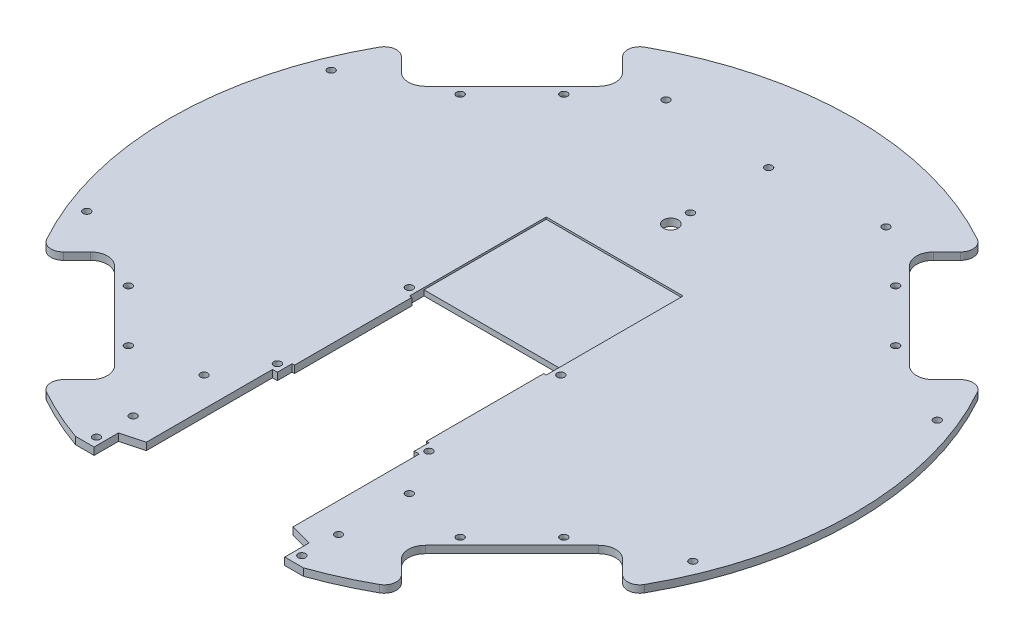
SolidWorks part; units mm, degrees
material "1060 Alloy"
ref_plane "Front Plane" through (0, 0, 0) normal (0, 0, 1) x (1, 0, 0)
ref_plane "Top Plane" through (0, 0, 0) normal (0, 1, 0) x (1, 0, 0)
ref_plane "Right Plane" through (0, 0, 0) normal (1, 0, 0) x (0, 0, -1)
sketch "Sketch1" plane through (0, 0, 0) normal (0, 1, 0) x (1, 0, 0)
  circle A0 centre (0, 0) radius 140
  dimension "D1" = 280
extrude "Boss-Extrude1" add sketch "Sketch1" along normal blind 3
sketch "Sketch7" plane through (0, 3, 0) normal (0, 1, 0) x (1, 0, 0)
  line L0 (-99.0303, -63.6043) -> (-63.6043, -99.0303)
  line L1 (-108.8591, -63.6043) -> (-121.6224, -76.3675)
  line L2 (-63.6043, -108.8591) -> (-76.3675, -121.6224)
  line L3 (-121.6224, -76.3675) -> (-76.3675, -121.6224)
  line L4 (0, 0) -> (-98.9949, -98.9949) construction
  line L7 (0, 0) -> (0, 130) construction
  circle A0 centre (0, 0) radius 140 construction
  arc A1 (-108.8591, -63.6043) -> (-99.0303, -63.6043) centre (-103.9447, -68.5186) cw
  arc A2 (-63.6043, -99.0303) -> (-63.6043, -108.8591) centre (-68.5186, -103.9447) cw
  dimension "D4" = 6.95
  dimension "D1" = 115
  dimension "D2" = 64
  dimension "D3" = 135
extrude "Cut-Extrude4" cut sketch "Sketch7" against normal up to next
sketch "Sketch9" plane through (0, 3, 0) normal (0, 1, 0) x (1, 0, 0)
  line L1 (-63.6043, -99.0303) -> (-99.0303, -63.6043) construction
  line L4 (-108.8591, -63.6043) -> (-119.0017, -73.7469) construction
  circle A0 centre (-89.0955, -67.8823) radius 1.5
  circle A1 centre (-67.8823, -89.0955) radius 1.5
  dimension "D4" = 3
  dimension "D1" = 4
  dimension "D2" = 30
  dimension "D3" = 17
  dimension "D5" = 4
extrude "Cut-Extrude6" cut sketch "Sketch9" against normal up to next
fillet "Fillet1" radius 5 2 edges at (-73.7469, 1.5, 119.0017) (-119.0017, 1.5, 73.7469)
pattern_circular "CirPattern1" count 4 over 360 about axis through (0, 3, 0) along (0, 1, 0) of "Cut-Extrude4", "Fillet1", "Cut-Extrude6"
sketch "Sketch2" plane through (0, 3, 0) normal (0, 1, 0) x (1, 0, 0)
  line L0 (-46.6476, -132) -> (-39, -132)
  line L1 (-30, -119.5885) -> (-30, -68)
  line L2 (-28, -8) -> (28, -8)
  line L3 (30, -68) -> (30, -119.5885)
  line L4 (39, -132) -> (46.6476, -132)
  line L5 (46.6476, -132) -> (46.6476, -140)
  line L6 (46.6476, -140) -> (-46.6476, -140)
  line L7 (-46.6476, -140) -> (-46.6476, -132)
  line L8 (-28, -62) -> (-28, -68)
  line L9 (-28, -68) -> (-30, -68)
  line L10 (28, -62) -> (28, -68)
  line L11 (28, -68) -> (30, -68)
  line L12 (-28, -62) -> (-27, -62)
  line L13 (-27, -62) -> (-27, -14)
  line L14 (-27, -14) -> (-28, -14)
  line L15 (-28, -14) -> (-28, -8)
  line L16 (28, -8) -> (28, -14)
  line L17 (28, -14) -> (27, -14)
  line L18 (27, -14) -> (27, -62)
  line L19 (27, -62) -> (28, -62)
  line L20 (-39, -132) -> (-39, -122)
  line L21 (-39, -122) -> (-30, -119.5885)
  line L22 (39, -132) -> (39, -122)
  line L23 (39, -122) -> (30, -119.5885)
  circle A0 centre (0, 0) radius 140 construction
  dimension "D8" = 1
  dimension "D5" = 60
  dimension "D6" = 56
  dimension "D1" = 8
  dimension "D2" = 124
  dimension "D3" = 60
  dimension "D4" = 16.6476
  dimension "D7" = 6
  dimension "D9" = 78
  dimension "D10" = 10
  dimension "D11" = 105
extrude "Cut-Extrude1" cut sketch "Sketch2" against normal up to next
fillet "Fillet3" radius 1.5 8 edges at (67.8823, 0, 90.5955) (89.0955, 0, 69.3823) (89.0955, 0, -66.3823) (67.8823, 0, -87.5955) (-67.8823, 0, -87.5955) (-89.0955, 0, -66.3823) (-67.8823, 0, 90.5955) (-89.0955, 0, 69.3823)
sketch "Sketch10" plane through (0, 3, 0) normal (0, 1, 0) x (1, 0, 0)
  circle A0 centre (-31, -65) radius 1.5
  circle A1 centre (31, -65) radius 1.5
  circle A2 centre (-31, -11) radius 1.5
  circle A3 centre (31, -11) radius 1.5
  dimension "D3" = 3
  dimension "D1" = 31
  dimension "D2" = 62
  dimension "D4" = 65
  dimension "D5" = 54
extrude "Cut-Extrude7" cut sketch "Sketch10" against normal up to next
sketch "Sketch13" plane through (0, 3, 0) normal (0, 1, 0) x (1, 0, 0)
  line L0 (-39, -132) -> (-46.6476, -132) construction
  line L1 (-39, -132) -> (-46.6476, -132) construction
  circle A0 centre (-42, -84) radius 1.5
  circle A1 centre (-42, -113) radius 1.5
  circle A2 centre (42, -113) radius 1.5
  circle A3 centre (42, -84) radius 1.5
  dimension "D1" = 3
  dimension "D2" = 19
  dimension "D3" = 48
  dimension "D4" = 42
  dimension "D5" = 42
extrude "Cut-Extrude9" cut sketch "Sketch13" against normal up to next
sketch "Sketch16" plane through (0, 3, 0) normal (0, 1, 0) x (1, 0, 0)
  circle A0 centre (0, 73) radius 1.5
  circle A1 centre (-45, 108) radius 1.5
  circle A2 centre (45, 108) radius 1.5
  circle A3 centre (0, 105) radius 1.5
  circle A4 centre (0, 65) radius 3
  dimension "D2" = 3
  dimension "D5" = 6
  dimension "D1" = 73
  dimension "D3" = 108
  dimension "D4" = 90
  dimension "D6" = 32
  dimension "D7" = 65
extrude "Cut-Extrude12" cut sketch "Sketch16" against normal up to next
sketch "Sketch17" plane through (0, 3, 0) normal (0, 1, 0) x (1, 0, 0)
  circle A0 centre (-124, 50) radius 1.5
  circle A1 centre (-124, -50) radius 1.5
  circle A2 centre (124, 50) radius 1.5
  circle A3 centre (124, -50) radius 1.5
  dimension "D1" = 3
  dimension "D2" = 50
  dimension "D3" = 50
  dimension "D4" = 124
  dimension "D5" = 124
extrude "Cut-Extrude13" cut sketch "Sketch17" against normal up to next
sketch "Sketch18" plane through (0, 3, 0) normal (0, 1, 0) x (1, 0, 0)
  line L0 (-28, -8) -> (-28, -14) construction
  line L1 (-28, -8) -> (28, -8)
  line L2 (-28, -8) -> (-28, 42)
  line L3 (-28, 42) -> (28, 42)
  line L4 (28, -8) -> (28, 42)
  line L5 (28, -8) -> (-28, -8) construction
  line L6 (28, -8) -> (-28, -8) construction
  dimension "D1" = 50
extrude "Cut-Extrude14" cut sketch "Sketch18" against normal blind 0.8
sketch "Sketch19" plane through (0, 3, 0) normal (0, 1, 0) x (1, 0, 0)
  line L0 (-39, -122) -> (-39, -132) construction
  line L1 (-39, -132) -> (-46.6476, -132) construction
  line L2 (39, -132) -> (39, -122) construction
  circle A0 centre (-42, -128) radius 1.5
  circle A1 centre (42, -128) radius 1.5
  dimension "D4" = 3
  dimension "D1" = 3
  dimension "D2" = 4
  dimension "D3" = 3
extrude "Cut-Extrude15" cut sketch "Sketch19" against normal up to next
